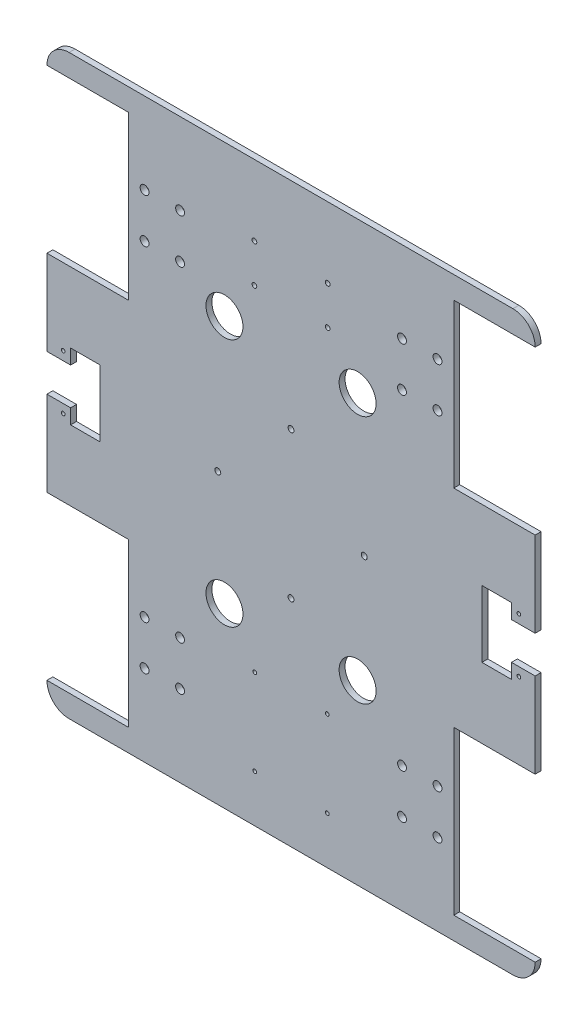
SolidWorks part; units mm, degrees
ref_plane "前视基准面" through (0, 0, 0) normal (0, 0, 1) x (1, 0, 0)
ref_plane "上视基准面" through (0, 0, 0) normal (0, 1, 0) x (1, 0, 0)
ref_plane "右视基准面" through (0, 0, 0) normal (1, 0, 0) x (0, 0, -1)
other "Configuration Table"
sketch "草图1" plane through (0, 0, 0) normal (0, 0, 1) x (1, 0, 0)
  line L1 (-165, 195) -> (165, 195)
  line L2 (-165, 195) -> (-165, -195)
  line L3 (-165, -195) -> (165, -195)
  line L4 (165, 195) -> (165, -195)
  line L5 (-165, 195) -> (165, -195) construction
  line L6 (-165, -195) -> (165, 195) construction
  point P0 (0, 0)
  dimension "D1" = 390
  dimension "D2" = 330
extrude "凸台-拉伸1" add sketch "草图1" along normal blind 4
sketch "草图3" plane through (0, 0, 4) normal (0, 0, 1) x (1, 0, 0)
  line L0 (0, 349.0758) -> (0, -226.6637) construction
  line L1 (110, 234.463) -> (110, -274.1029) construction
  line L6 (-110, 234.463) -> (-110, -274.1029) construction
  line L7 (165, -195) -> (165, 195) construction
  line L8 (220, 70) -> (110, 70)
  line L9 (220, 70) -> (220, 180)
  line L10 (220, 180) -> (110, 180)
  line L11 (110, 70) -> (110, 180)
  line L12 (220, 70) -> (110, 180) construction
  line L13 (220, 180) -> (110, 70) construction
  line L15 (220, -180) -> (110, -180)
  line L16 (220, -180) -> (220, -70)
  line L17 (220, -70) -> (110, -70)
  line L18 (110, -180) -> (110, -70)
  line L19 (220, -180) -> (110, -70) construction
  line L20 (220, -70) -> (110, -180) construction
  line L21 (-165, -195) -> (165, -195) construction
  line L24 (-220, -70) -> (-110, -180) construction
  line L25 (-220, -180) -> (-110, -70) construction
  line L26 (-110, 234.463) -> (-110, -274.1029) construction
  line L27 (-110, -180) -> (-110, -70)
  line L28 (-220, -70) -> (-110, -70)
  line L29 (-220, -180) -> (-220, -70)
  line L30 (-220, -180) -> (-110, -180)
  line L31 (-110, 70) -> (-110, 180)
  line L32 (-220, 180) -> (-110, 180)
  line L33 (-220, 70) -> (-220, 180)
  line L34 (-220, 70) -> (-110, 70)
  point P7 (165, 125)
  point P15 (165, -125)
  point P26 (-165, -125)
  dimension "D1" = 110
  dimension "D2" = 110
  dimension "D3" = 110
  dimension "D4" = 140
  dimension "D5" = 15
extrude "切除-拉伸1" cut sketch "草图3" against normal blind 4
sketch "草图5" plane through (0, 0, 4) normal (0, 0, 1) x (1, 0, 0)
  line L0 (0, 0) -> (0, -375.4481) construction
  line L1 (-165, -195) -> (165, -195) construction
  line L2 (-24.5, -105) -> (24.5, -105) construction
  line L3 (-24.5, -105) -> (-24.5, -163) construction
  line L4 (-24.5, -163) -> (24.5, -163) construction
  line L5 (24.5, -105) -> (24.5, -163) construction
  line L6 (-24.5, -105) -> (24.5, -163) construction
  line L7 (-24.5, -163) -> (24.5, -105) construction
  circle A0 centre (24.5, -163) radius 1.25
  circle A1 centre (24.5, -105) radius 1.25
  circle A2 centre (-24.5, -105) radius 1.25
  circle A3 centre (-24.5, -163) radius 1.25
  point P3 (0, -134)
  dimension "D4" = 2.5
  dimension "D5" = 2.5
  dimension "D1" = 58
  dimension "D2" = 49
  dimension "D3" = 90
extrude "切除-拉伸2" cut sketch "草图5" against normal blind 4
sketch "草图7" plane through (0, 0, 4) normal (0, 0, 1) x (1, 0, 0)
  line L1 (0, 0) -> (64.6599, 0) construction
  line L5 (0, 49.5011) -> (-49.5011, 0.0072) construction
  line L6 (-49.5011, 0.0072) -> (-0.0072, -49.4939) construction
  line L7 (-0.0072, -49.4939) -> (49.4939, 0) construction
  line L8 (49.4939, 0) -> (0, 49.5011) construction
  line L9 (0, 0) -> (0, 79.6336) construction
  circle A1 centre (49.4939, 0) radius 2
  circle A2 centre (-49.5011, 0.0072) radius 2
  circle A3 centre (0, 49.5011) radius 2
  circle A4 centre (-0.0072, -49.4939) radius 2
  dimension "D1" = 4
  dimension "D2" = 4
  dimension "D3" = 4
  dimension "D4" = 4
  dimension "D5" = 70
  dimension "D6" = 70
extrude "切除-拉伸3" cut sketch "草图7" against normal blind 4
sketch "草图8" plane through (0, 0, 4) normal (0, 0, 1) x (1, 0, 0)
  line L0 (0, 165.5293) -> (0, 0) construction
  line L2 (-24.75, 147.2595) -> (24.75, 147.2595) construction
  line L3 (-24.75, 147.2595) -> (-24.75, 121.2595) construction
  line L4 (-24.75, 121.2595) -> (24.75, 121.2595) construction
  line L5 (24.75, 147.2595) -> (24.75, 121.2595) construction
  line L6 (-24.75, 147.2595) -> (24.75, 121.2595) construction
  line L7 (-24.75, 121.2595) -> (24.75, 147.2595) construction
  circle A0 centre (24.75, 121.2595) radius 1.6
  circle A1 centre (24.75, 147.2595) radius 1.6
  circle A2 centre (-24.75, 147.2595) radius 1.6
  circle A3 centre (-24.75, 121.2595) radius 1.6
  point P3 (0, 134.2595)
  dimension "D3" = 3.2
  dimension "D4" = 3.2
  dimension "D1" = 26
  dimension "D2" = 49.5
extrude "切除-拉伸4" cut sketch "草图8" against normal blind 4
sketch "草图9" plane through (0, 0, 4) normal (0, 0, 1) x (1, 0, 0)
  line L0 (40.9206, -125) -> (239.6376, -125) construction
  line L1 (165, -70) -> (110, -70) construction
  line L4 (153, -145) -> (67, -145) construction
  line L5 (153, -145) -> (153, -105) construction
  line L6 (153, -105) -> (67, -105) construction
  line L7 (67, -145) -> (67, -105) construction
  line L8 (153, -145) -> (67, -105) construction
  line L9 (153, -105) -> (67, -145) construction
  line L10 (110, -70) -> (110, -180) construction
  line L11 (0, 0) -> (0, -264.1351) construction
  line L12 (75, -140) -> (99, -140) construction
  line L13 (75, -140) -> (75, -110) construction
  line L14 (75, -110) -> (99, -110) construction
  line L15 (99, -140) -> (99, -110) construction
  line L16 (75, -140) -> (99, -110) construction
  line L17 (75, -110) -> (99, -140) construction
  circle A0 centre (99, -140) radius 3
  circle A1 centre (75, -140) radius 3
  circle A2 centre (99, -110) radius 3
  circle A3 centre (75, -110) radius 3
  circle A4 centre (-99, -110) radius 3
  circle A5 centre (-75, -110) radius 3
  circle A6 centre (-99, -140) radius 3
  circle A7 centre (-75, -140) radius 3
  point P4 (110, -125)
  point P11 (87, -125)
  dimension "D8" = 6
  dimension "D9" = 6
  dimension "D1" = 55
  dimension "D2" = 40
  dimension "D3" = 43
  dimension "D4" = 43
  dimension "D5" = 30
  dimension "D6" = 24
  dimension "D7" = 8
extrude "切除-拉伸5" cut sketch "草图9" against normal blind 4
sketch "草图11" plane through (0, 0, 4) normal (0, 0, 1) x (1, 0, 0)
  line L0 (0, 125) -> (154.4147, 125) construction
  line L1 (0, 125) -> (0, 0) construction
  line L2 (110, 70) -> (165, 70) construction
  line L3 (67, 149.7791) -> (67, 98.1981) construction
  line L4 (110, 180) -> (110, 70) construction
  line L6 (75, 110) -> (99, 110) construction
  line L7 (75, 110) -> (75, 140) construction
  line L8 (75, 140) -> (99, 140) construction
  line L9 (99, 110) -> (99, 140) construction
  line L10 (75, 110) -> (99, 140) construction
  line L11 (75, 140) -> (99, 110) construction
  circle A0 centre (99, 140) radius 3
  circle A1 centre (99, 110) radius 3
  circle A2 centre (75, 110) radius 3
  circle A3 centre (75, 140) radius 3
  circle A4 centre (-75, 110) radius 3
  circle A5 centre (-99, 110) radius 3
  circle A6 centre (-99, 140) radius 3
  circle A7 centre (-75, 140) radius 3
  point P10 (87, 125)
  dimension "D6" = 6
  dimension "D7" = 6
  dimension "D8" = 6
  dimension "D9" = 6
  dimension "D1" = 55
  dimension "D2" = 43
  dimension "D3" = 30
  dimension "D4" = 24
  dimension "D5" = 8
extrude "切除-拉伸6" cut sketch "草图11" against normal blind 4
sketch "草图14" plane through (0, 0, 4) normal (0, 0, 1) x (1, 0, 0)
  line L0 (0, 110.7295) -> (0, -35.5916) construction
  circle A0 centre (45, 93.1712) radius 12.5
  circle A1 centre (45, -75.0521) radius 12.5
  circle A2 centre (-45, -75.0521) radius 12.5
  circle A3 centre (-45, 93.1712) radius 12.5
  point P11 (41.9679, -75.0521)
  point P12 (41.9679, 93.1712)
  dimension "D1" = 25
  dimension "D2" = 25
  dimension "D3" = 45
  dimension "D4" = 45
extrude "切除-拉伸7" cut sketch "草图14" against normal blind 4
fillet "圆角1" radius 15 4 edges at (165, -195, 2) (-165, -195, 2) (165, 195, 2) (-165, 195, 2)
sketch "草图15" plane through (0, 0, 4) normal (0, 0, 1) x (1, 0, 0)
  line L0 (0, 0) -> (250.5705, 0) construction
  line L1 (154, 41.1171) -> (154, -56.7935) construction
  line L2 (165, -70) -> (165, 70) construction
  circle A0 centre (154, 18.45) radius 1.25
  circle A1 centre (154, -18.3424) radius 1.25
  dimension "D2" = 2.5
  dimension "D3" = 36.9
  dimension "D4" = 2.5
  dimension "D1" = 11
extrude "切除-拉伸8" cut sketch "草图15" against normal blind 4
sketch "草图16" plane through (0, 0, 4) normal (0, 0, 1) x (1, 0, 0)
  line L0 (56.2122, 0) -> (239.851, 0) construction
  line L1 (165, -12.5) -> (165, 12.5)
  line L2 (165, -70) -> (165, 70) construction
  line L3 (165, 12.5) -> (149, 12.5)
  line L4 (149, 12.5) -> (149, 22.5)
  line L5 (149, 22.5) -> (129, 22.5)
  line L6 (129, 22.5) -> (129, -22.5)
  line L7 (149, -12.5) -> (149, -22.5)
  line L8 (149, -22.5) -> (129, -22.5)
  line L9 (165, -12.5) -> (149, -12.5)
  point P11 (129, 0)
  point P14 (165, 0)
  dimension "D1" = 25
  dimension "D2" = 45
  dimension "D3" = 16
  dimension "D4" = 20
extrude "切除-拉伸9" cut sketch "草图16" against normal blind 4
mirror "镜向1" about plane through (0, 0, 0) normal (1, 0, 0) of "切除-拉伸9", "切除-拉伸8"
